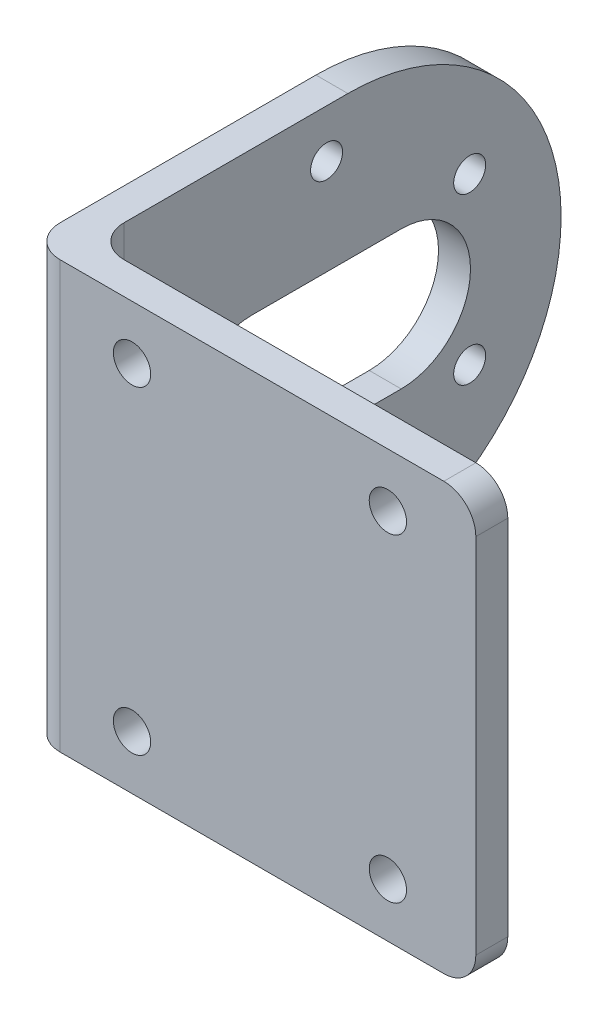
SolidWorks part; units mm, degrees
ref_plane "Front Plane" through (0, 0, 0) normal (0, 0, 1) x (1, 0, 0)
ref_plane "Top Plane" through (0, 0, 0) normal (0, 1, 0) x (1, 0, 0)
ref_plane "Right Plane" through (0, 0, 0) normal (1, 0, 0) x (0, 0, -1)
sketch "Schizzo1" plane through (0, 0, 0) normal (0, 1, 0) x (1, 0, 0)
  line L0 (0, 0) -> (0, 47)
  line L1 (0, 0) -> (42, 0)
  line L2 (3, 3) -> (3, 47)
  line L3 (3, 3) -> (42, 3)
  line L4 (0, 47) -> (3, 47)
  line L5 (42, 3) -> (42, 0)
  dimension "D1" = 47
  dimension "D2" = 42
  dimension "D3" = 3
extrude "Estrusione-Estrusione1" add sketch "Schizzo1" along normal blind 40
sketch "Schizzo2" plane through (3, 0, 0) normal (1, 0, 0) x (0, 0, -1)
  line L0 (3, 0) -> (47, 0) construction
  line L1 (47, 40) -> (47, 0) construction
  line L2 (18, 20) -> (32, 20) construction
  line L3 (18, 26.5) -> (32, 26.5)
  line L4 (18, 13.5) -> (32, 13.5)
  circle A0 centre (25, 20) radius 15.5 construction
  circle A1 centre (25, 4.5) radius 1.5
  circle A2 centre (11.5766, 12.25) radius 1.5
  circle A3 centre (11.5766, 27.75) radius 1.5
  circle A4 centre (25, 35.5) radius 1.5
  circle A5 centre (38.4234, 27.75) radius 1.5
  circle A6 centre (38.4234, 12.25) radius 1.5
  arc A7 (18, 26.5) -> (18, 13.5) centre (18, 20) ccw
  arc A8 (32, 13.5) -> (32, 26.5) centre (32, 20) ccw
  point P5 (25, 0)
  point P9 (47, 20)
  point P22 (25, 20)
  dimension "D1" = 31
  dimension "D2" = 3
  dimension "D4" = 13
  dimension "D5" = 14
  dimension "D3" = 6
extrude "Taglio-Estrusione1" cut sketch "Schizzo2" against normal through all
fillet "Raccordo1" radius 3 2 edges at (0, 20, 0) (3, 20, -3)
fillet "Raccordo2" radius 20 2 edges at (1.5, 0, -47) (1.5, 40, -47)
sketch "Schizzo3" plane through (0, 0, -3) normal (0, 0, -1) x (-1, 0, 0)
  line L0 (-42, 40) -> (-6, 40) construction
  line L1 (-42, 40) -> (-42, 0) construction
  line L2 (-42, 20) -> (-30.0988, 20) construction
  circle A0 centre (-33.75, 34.95) radius 1.75
  circle A1 centre (-9.75, 34.95) radius 1.75
  circle A2 centre (-9.75, 5.05) radius 1.75
  circle A3 centre (-33.75, 5.05) radius 1.75
  dimension "D1" = 5.05
  dimension "D2" = 3.5
  dimension "D3" = 8.25
  dimension "D4" = 24
extrude "Taglio-Estrusione2" cut sketch "Schizzo3" against normal through all
fillet "Raccordo3" radius 3 2 edges at (42, 0, -1.5) (42, 40, -1.5)
